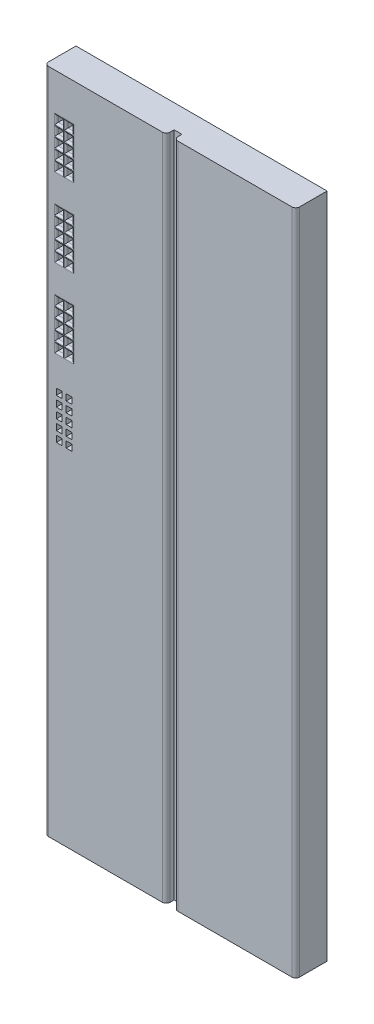
SolidWorks part; units mm, degrees
ref_plane "Plano frontal" through (0, 0, 0) normal (0, 0, 1) x (1, 0, 0)
ref_plane "Plano superior" through (0, 0, 0) normal (0, 1, 0) x (1, 0, 0)
ref_plane "Plano direito" through (0, 0, 0) normal (1, 0, 0) x (0, 0, -1)
sketch "Esboço1" plane through (0, 0, 0) normal (0, 0, 1) x (1, 0, 0)
  line L1 (0, 0) -> (64, 0)
  line L2 (0, 0) -> (0, 170)
  line L3 (0, 170) -> (64, 170)
  line L4 (64, 0) -> (64, 170)
  dimension "D1" = 170
  dimension "D2" = 64
extrude "Ressalto-extrusão1" add sketch "Esboço1" along normal blind 8
sketch "Esboço2" plane through (0, 0, 8) normal (0, 0, 1) x (1, 0, 0)
  line L0 (5, 170) -> (5, 0) construction
  line L1 (64, 170) -> (0, 170) construction
  line L2 (0, 0) -> (64, 0) construction
  line L3 (59, 170) -> (59, 0) construction
  line L4 (23, 170) -> (23, -2.4578) construction
  line L5 (41, 170) -> (41, 0) construction
  line L6 (0, 170) -> (0, 0) construction
  line L7 (64, 0) -> (64, 170) construction
  line L8 (4.5, 160) -> (4.5, 148)
  line L9 (3, 160) -> (7, 160)
  line L10 (3, 160) -> (3, 148)
  line L11 (3, 148) -> (7, 148)
  line L12 (7, 160) -> (7, 148)
  line L13 (5.5, 160) -> (5.5, 148)
  line L14 (3, 158.4) -> (7, 158.4)
  line L15 (3, 152.2) -> (7, 152.2)
  line L16 (3, 150.6) -> (7, 150.6)
  line L17 (3, 149.6) -> (7, 149.6)
  line L18 (3, 153.2) -> (7, 153.2)
  line L19 (3, 154.8) -> (7, 154.8)
  line L20 (3, 155.8) -> (7, 155.8)
  line L21 (3, 157.4) -> (7, 157.4)
  line L22 (3, 134.8) -> (7, 134.8)
  line L23 (3, 140) -> (7, 140)
  line L24 (3, 140) -> (3, 128)
  line L25 (7, 140) -> (7, 128)
  line L26 (3, 132.2) -> (7, 132.2)
  line L27 (3, 133.2) -> (7, 133.2)
  line L28 (5.5, 140) -> (5.5, 128)
  line L29 (3, 137.4) -> (7, 137.4)
  line L30 (3, 128) -> (7, 128)
  line L31 (3, 130.6) -> (7, 130.6)
  line L32 (3, 138.4) -> (7, 138.4)
  line L33 (3, 129.6) -> (7, 129.6)
  line L34 (3, 135.8) -> (7, 135.8)
  line L35 (4.5, 140) -> (4.5, 128)
  line L36 (3, 114.8) -> (7, 114.8)
  line L37 (3, 120) -> (7, 120)
  line L38 (3, 120) -> (3, 108)
  line L39 (7, 120) -> (7, 108)
  line L40 (3, 112.2) -> (7, 112.2)
  line L41 (3, 113.2) -> (7, 113.2)
  line L42 (5.5, 120) -> (5.5, 108)
  line L43 (3, 117.4) -> (7, 117.4)
  line L44 (3, 108) -> (7, 108)
  line L45 (3, 110.6) -> (7, 110.6)
  line L46 (3, 118.4) -> (7, 118.4)
  line L47 (3, 109.6) -> (7, 109.6)
  line L48 (3, 115.8) -> (7, 115.8)
  line L49 (4.5, 120) -> (4.5, 108)
  line L50 (3, 94.8) -> (7, 94.8)
  line L51 (3, 100) -> (7, 100)
  line L52 (3, 100) -> (3, 88)
  line L53 (7, 100) -> (7, 88)
  line L54 (3, 92.2) -> (7, 92.2)
  line L55 (3, 93.2) -> (7, 93.2)
  line L56 (5.5, 100) -> (5.5, 88)
  line L57 (3, 97.4) -> (7, 97.4)
  line L58 (3, 88) -> (7, 88)
  line L59 (3, 90.6) -> (7, 90.6)
  line L60 (3, 98.4) -> (7, 98.4)
  line L61 (3, 89.6) -> (7, 89.6)
  line L62 (3, 95.8) -> (7, 95.8)
  line L63 (4.5, 100) -> (4.5, 88)
  point P20 (5, 160)
  dimension "D1" = 5
  dimension "D2" = 5
  dimension "D3" = 23
  dimension "D4" = 23
  dimension "D5" = 12
  dimension "D6" = 4
  dimension "D7" = 10
  dimension "D8" = 1.5
  dimension "D9" = 1.5
  dimension "D10" = 1.6
  dimension "D11" = 1.6
  dimension "D12" = 1.6
  dimension "D13" = 1
  dimension "D14" = 1
  dimension "D15" = 1.6
  dimension "D16" = 1
  dimension "D17" = 1
  dimension "D18" = 12
  dimension "D19" = 4
  dimension "D20" = 1.5
  dimension "D21" = 1.5
  dimension "D22" = 1.6
  dimension "D23" = 1.6
  dimension "D24" = 1.6
  dimension "D25" = 1
  dimension "D26" = 1
  dimension "D27" = 1.6
  dimension "D28" = 1
  dimension "D29" = 1
  dimension "D30" = 12
  dimension "D31" = 4
  dimension "D32" = 1.5
  dimension "D33" = 1.5
  dimension "D34" = 1.6
  dimension "D35" = 1.6
  dimension "D36" = 1.6
  dimension "D37" = 1
  dimension "D38" = 1
  dimension "D39" = 1.6
  dimension "D40" = 1
  dimension "D41" = 1
  dimension "D42" = 12
  dimension "D43" = 4
  dimension "D44" = 1.5
  dimension "D45" = 1.5
  dimension "D46" = 1.6
  dimension "D47" = 1.6
  dimension "D48" = 1.6
  dimension "D49" = 1
  dimension "D50" = 1
  dimension "D51" = 1.6
  dimension "D52" = 1
  dimension "D53" = 1
sketch "Esboço3" plane through (0, 0, 0) normal (0, -1, 0) x (1, 0, 0)
  line L0 (0, 8) -> (64, 8) construction
  line L1 (31, 8) -> (33, 8)
  line L2 (31, 8) -> (31, 6)
  line L3 (31, 6) -> (33, 6)
  line L4 (33, 8) -> (33, 6)
  point P4 (32, 8)
  point P7 (32, 8)
  dimension "D1" = 2
  dimension "D2" = 2
extrude "Corte-extrusão1" cut sketch "Esboço3" against normal through all
fillet "Filete1" radius 1 4 edges at (31, 85, 8) (33, 85, 8) (64, 85, 8) (0, 85, 8)
extrude "Corte-extrusão2" cut sketch "Esboço2" against normal mid plane 8 contours L17 L10 L11 L8 | L17 L13 L11 L12 | L13 L16 L12 L15 | L10 L16 L8 L15 | L19 L10 L18 L8 | L19 L13 L18 L12 | L21 L13 L20 L12 | L21 L10 L20 L8 | L10 L14 L8 L9 | L13 L14 L12 L9 region at (3.75, 159.2, 8) region at (6.25, 159.2, 8) region at (3.75, 156.6, 8) region at (6.25, 156.6, 8) region at (3.75, 154, 8) region at (6.25, 154, 8) region at (3.75, 151.4, 8) region at (6.25, 151.4, 8) region at (3.75, 148.8, 8) region at (6.25, 148.8, 8)
fillet "Filete2" radius 0.5 40 edges at (4.5, 148.8, 8) (3.75, 148, 8) (6.25, 148, 8) (7, 148.8, 8) (5.5, 148.8, 8) (6.25, 149.6, 8) (3.75, 149.6, 8) (3, 148.8, 8) (3.75, 150.6, 8) (3, 151.4, 8) (3.75, 152.2, 8) (4.5, 151.4, 8) (6.25, 150.6, 8) (7, 151.4, 8) (5.5, 151.4, 8) (6.25, 152.2, 8) (3, 154, 8) (3.75, 154.8, 8) (4.5, 154, 8) (6.25, 153.2, 8) (7, 154, 8) (6.25, 154.8, 8) (5.5, 154, 8) (6.25, 155.8, 8) (3.75, 155.8, 8) (3, 156.6, 8) (4.5, 156.6, 8) (5.5, 156.6, 8) (7, 156.6, 8) (6.25, 157.4, 8) (3.75, 157.4, 8) (6.25, 158.4, 8) (7, 159.2, 8) (6.25, 160, 8) (5.5, 159.2, 8) (3.75, 158.4, 8) (3, 159.2, 8) (4.5, 159.2, 8) (3.75, 160, 8) (3.75, 153.2, 8)
extrude "Corte-extrusão3" cut sketch "Esboço2<7>" against normal mid plane 8 contours L35 L33 L24 L30 | L33 L28 L30 L25 | L35 L26 L24 L31 | L28 L31 L25 L26 | L35 L22 L24 L27 | L22 L28 L27 L25 | L35 L29 L24 L34 | L28 L34 L25 L29 | L35 L23 L24 L32 | L28 L32 L25 L23 | L49 L47 L38 L44 | L47 L42 L44 L39 | L49 L40 L38 L45 | L42 L45 L39 L40 | L49 L36 L38 L41 | L36 L42 L41 L39 | L49 L43 L38 L48 | L42 L48 L39 L43 | L49 L37 L38 L46 | L42 L46 L39 L37 | L61 L56 L58 L53 | L63 L61 L52 L58 | L63 L54 L52 L59 | L56 L59 L53 L54 | L63 L50 L52 L55 | L50 L56 L55 L53 | L63 L57 L52 L62 | L56 L62 L53 L57 | L63 L51 L52 L60 | L56 L60 L53 L51 region at (3.75, 134, 8) region at (3.75, 136.6, 8) region at (6.25, 134, 8) region at (3.75, 131.4, 8) region at (6.25, 136.6, 8) region at (3.75, 139.2, 8) region at (6.25, 131.4, 8) region at (3.75, 128.8, 8) region at (6.25, 139.2, 8) region at (6.25, 128.8, 8) region at (3.75, 114, 8) region at (3.75, 116.6, 8) region at (6.25, 114, 8) region at (3.75, 111.4, 8) region at (6.25, 116.6, 8) region at (3.75, 119.2, 8) region at (6.25, 111.4, 8) region at (3.75, 108.8, 8) region at (6.25, 119.2, 8) region at (6.25, 108.8, 8) region at (3.75, 94, 8) region at (3.75, 96.6, 8) region at (6.25, 94, 8) region at (3.75, 91.4, 8) region at (6.25, 96.6, 8) region at (3.75, 99.2, 8) region at (6.25, 91.4, 8) region at (3.75, 88.8, 8) region at (6.25, 99.2, 8) region at (6.25, 88.8, 8)
sketch "Esboço2<7>" plane through (0, 0, 8) normal (0, 0, 1) x (1, 0, 0) same geometry as "Esboço2"
fillet "Filete3" radius 0.5 80 edges at (5.5, 108.8, 8) (6.25, 109.6, 8) (7, 108.8, 8) (6.25, 108, 8) (3.75, 108, 8) (4.5, 108.8, 8) (3, 108.8, 8) (3.75, 109.6, 8) (4.5, 111.4, 8) (3.75, 110.6, 8) (3, 111.4, 8) (3.75, 112.2, 8) (6.25, 112.2, 8) (5.5, 111.4, 8) (6.25, 110.6, 8) (7, 111.4, 8) (3, 114, 8) (3.75, 114.8, 8) (4.5, 114, 8) (3.75, 113.2, 8) (6.25, 113.2, 8) (7, 114, 8) (5.5, 114, 8) (6.25, 114.8, 8) (6.25, 115.8, 8) (7, 116.6, 8) (5.5, 116.6, 8) (6.25, 117.4, 8) (3.75, 115.8, 8) (4.5, 116.6, 8) (3, 116.6, 8) (3.75, 117.4, 8) (5.5, 119.2, 8) (6.25, 120, 8) (7, 119.2, 8) (6.25, 118.4, 8) (3.75, 118.4, 8) (4.5, 119.2, 8) (3, 119.2, 8) (3.75, 120, 8) (3.75, 128, 8) (5.5, 128.8, 8) (6.25, 128, 8) (7, 128.8, 8) (6.25, 129.6, 8) (4.5, 128.8, 8) (3, 128.8, 8) (3.75, 129.6, 8) (3.75, 130.6, 8) (6.25, 130.6, 8) (7, 131.4, 8) (5.5, 131.4, 8) (6.25, 132.2, 8) (4.5, 131.4, 8) (3, 131.4, 8) (3.75, 132.2, 8) (3.75, 133.2, 8) (6.25, 133.2, 8) (7, 134, 8) (5.5, 134, 8) (6.25, 134.8, 8) (4.5, 134, 8) (3, 134, 8) (3.75, 134.8, 8) (3.75, 135.8, 8) (3, 136.6, 8) (3.75, 137.4, 8) (4.5, 136.6, 8) (5.5, 136.6, 8) (6.25, 135.8, 8) (7, 136.6, 8) (6.25, 137.4, 8) (6.25, 138.4, 8) (7, 139.2, 8) (6.25, 140, 8) (5.5, 139.2, 8) (3.75, 138.4, 8) (3, 139.2, 8) (4.5, 139.2, 8) (3.75, 140, 8)
